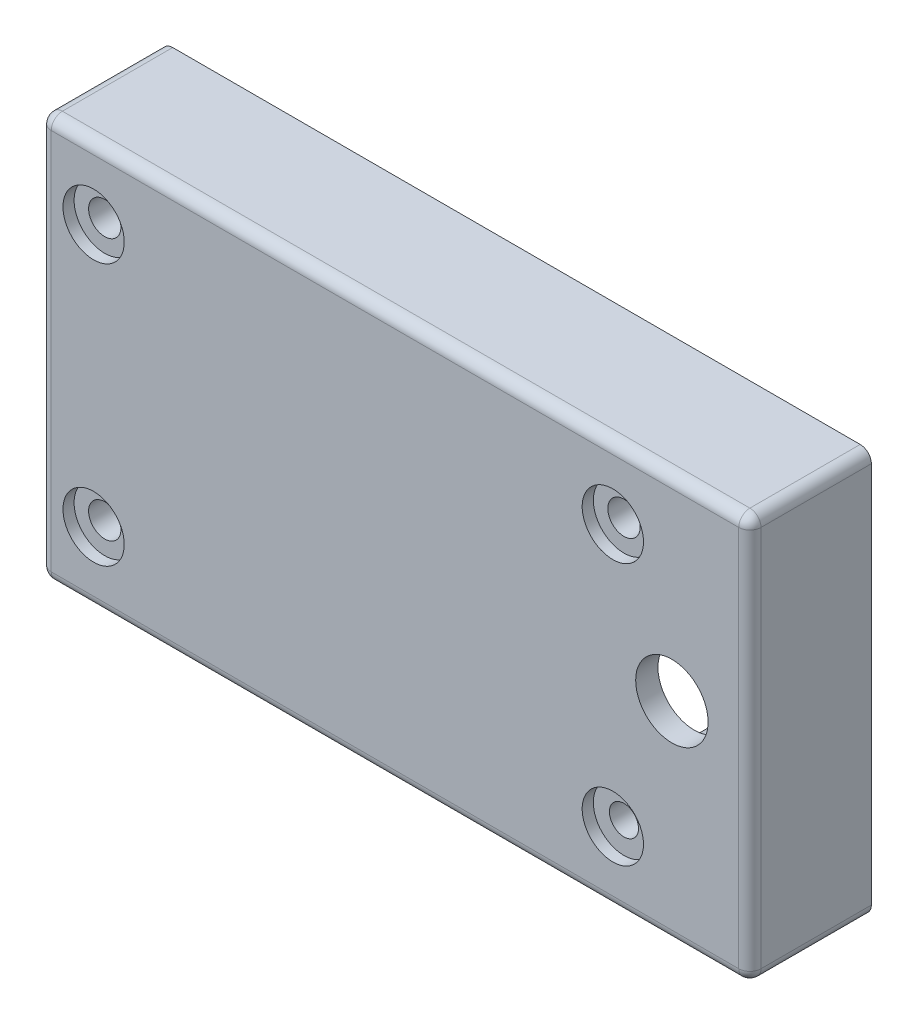
SolidWorks part; units mm, degrees
ref_plane "Alzado" through (0, 0, 0) normal (0, 0, 1) x (1, 0, 0)
ref_plane "Planta" through (0, 0, 0) normal (0, 1, 0) x (1, 0, 0)
ref_plane "Vista lateral" through (0, 0, 0) normal (1, 0, 0) x (0, 0, -1)
sketch "Croquis1" plane through (0, 0, 0) normal (0, 0, 1) x (1, 0, 0)
  line L0 (-27.2842, -16.3489) -> (32.4158, -16.3489) construction
  line L1 (-29.2842, -18.3489) -> (34.4158, -18.3489)
  line L2 (-29.2842, -18.3489) -> (-29.2842, 17.9511)
  line L3 (-29.2842, 17.9511) -> (34.4158, 17.9511)
  line L4 (34.4158, -18.3489) -> (34.4158, 17.9511)
  line L5 (32.4158, -16.3489) -> (-27.2842, -16.3489)
  line L6 (32.4158, -16.3489) -> (32.4158, 15.9511)
  line L7 (32.4158, 15.9511) -> (-27.2842, 15.9511)
  line L8 (-27.2842, -16.3489) -> (-27.2842, 15.9511)
  line L9 (32.4158, -16.3489) -> (32.4158, 15.9511) construction
sketch "Croquis2" plane through (-1.3633, 4.2361, 1) normal (0, 0, 1) x (0, 1, 0)
  circle A0 centre (-16.185, 23.1209) radius 1.45
  circle A1 centre (-16.185, 23.1209) radius 2.4
  circle A2 centre (7.315, 23.1209) radius 1.45
  circle A3 centre (7.315, 23.1209) radius 2.4
  circle A4 centre (7.315, -23.4791) radius 1.45
  circle A5 centre (7.315, -23.4791) radius 2.2627
  circle A6 centre (-16.185, -23.4791) radius 1.3049
  circle A7 centre (-16.185, -23.4791) radius 2.4
extrude "Saliente-Extruir2" add sketch "Croquis2" against normal up to surface (12.3 mm away) separate body
sketch "Croquis4" plane through (-1.3633, 4.2361, 1) normal (0, 0, 1) x (0, 1, 0)
  line L0 (-20.585, -33.7791) -> (11.715, -33.7791) construction
  line L1 (13.715, 27.9209) -> (-22.585, 27.9209)
  line L2 (13.715, 27.9209) -> (13.715, -35.7791)
  line L3 (13.715, -35.7791) -> (-22.585, -35.7791)
  line L4 (-22.585, 27.9209) -> (-22.585, -35.7791)
  line L5 (-20.585, -33.7791) -> (11.715, -33.7791)
  line L6 (-20.585, -33.7791) -> (-20.585, 25.9209)
  line L7 (-20.585, 25.9209) -> (11.715, 25.9209)
  line L8 (11.715, -33.7791) -> (11.715, 25.9209)
  line L9 (-20.585, 25.9209) -> (-20.585, -33.7791) construction
extrude "Saliente-Extruir4" add sketch "Croquis4" against normal up to surface (8.9 mm away) separate body
sketch "Croquis5" plane through (-1.3633, 4.2361, 1) normal (0, 0, 1) x (0, 1, 0)
  line L1 (-22.585, 27.9209) -> (13.715, 27.9209)
  line L2 (-22.585, 27.9209) -> (-22.585, -35.7791)
  line L3 (-22.585, -35.7791) -> (13.715, -35.7791)
  line L4 (13.715, 27.9209) -> (13.715, -35.7791)
extrude "Saliente-Extruir5" add sketch "Croquis5" along normal blind 2
fillet "Redondeo1" radius 1 8 edges at (-29.2842, -0.1989, 3) (2.5658, 17.9511, 3) (34.4158, -0.1989, 3) (2.5658, -18.3489, 3) (34.4158, -18.3489, -2.45) (34.4158, 17.9511, -2.45) (-29.2842, 17.9511, -2.45) (-29.2842, -18.3489, -2.45)
sketch "Croquis6" plane through (-29.2842, 0, 0) normal (-1, 0, 0) x (0, 0, 1)
  line L0 (-7.9, -17.3489) -> (-7.9, 16.9511) construction
  line L1 (-7.9, -5.7361) -> (-6.9475, -5.7361)
  line L2 (-7.9, -5.7361) -> (-7.9, 5.2936)
  line L3 (-7.9, 5.2936) -> (-6.9475, 5.2936)
  line L4 (-6.9475, -5.7361) -> (-6.9475, 5.2936)
  line L5 (-12.7896, -5.7361) -> (-7.9, -5.7361) construction
extrude "Cortar-Extruir1" cut sketch "Croquis6" against normal blind 1
fillet "Redondeo2" radius 1 3 edges at (-29.2842, -5.7361, -7.4238) (-29.2842, 5.2936, -7.4238) (-29.2842, -0.2212, -6.9475)
sketch "Croquis7" plane through (0, 0, -11.3) normal (0, 0, -1) x (-1, 0, 0)
  circle A0 centre (24.4842, 11.5511) radius 1.45
  circle A1 centre (24.4842, -11.9489) radius 1.45
  circle A2 centre (-22.1158, -11.9489) radius 1.3049
  circle A3 centre (-22.1158, 11.5511) radius 1.45
extrude "Cortar-Extruir2" cut sketch "Croquis7" against normal through all
sketch "Croquis8" plane through (0, 0, 3) normal (0, 0, 1) x (1, 0, 0)
  circle A0 centre (-24.4842, -11.9489) radius 2.75
  circle A1 centre (-24.4842, 11.5511) radius 2.75
  circle A2 centre (22.1158, -11.9489) radius 2.75
  circle A3 centre (22.1158, 11.5511) radius 2.75
  dimension "D1" = 5.5
  dimension "D2" = 5.5
  dimension "D3" = 5.5
  dimension "D4" = 5.5
extrude "Cortar-Extruir3" cut sketch "Croquis8" against normal blind 1
sketch "Croquis9" plane through (0, 0, 1) normal (0, 0, -1) x (-1, 0, 0)
  line L0 (-32.4158, -16.3489) -> (-32.4158, 15.9511) construction
  line L9 (-32.4158, 15.9511) -> (27.2842, 15.9511) construction
  circle A0 centre (-27.4158, 0.4511) radius 3.2502
  dimension "D1" = 6.5004
  dimension "D2" = 5
  dimension "D3" = 15.5
extrude "Cortar-Extruir4" cut sketch "Croquis9" against normal through all
sketch "Croquis10" plane through (0, 0, 1) normal (0, 0, -1) x (-1, 0, 0)
  line L17 (-14.0598, 10.3107) -> (14.5295, 10.3107)
  line L18 (-14.0598, 10.3107) -> (-14.0598, -10.3255)
  line L19 (-14.0598, -10.3255) -> (14.5295, -10.3255)
  line L20 (14.5295, 10.3107) -> (14.5295, -10.3255)
  line L21 (-15.0598, 11.3107) -> (15.5295, 11.3107)
  line L22 (-15.0598, 11.3107) -> (-15.0598, -11.3255)
  line L23 (-15.0598, -11.3255) -> (15.5295, -11.3255)
  line L24 (15.5295, 11.3107) -> (15.5295, -11.3255)
  dimension "D1" = 1
  dimension "D2" = 1
  dimension "D3" = 1
  dimension "D4" = 1
extrude "Saliente-Extruir6" add sketch "Croquis10" along normal blind 2.5
